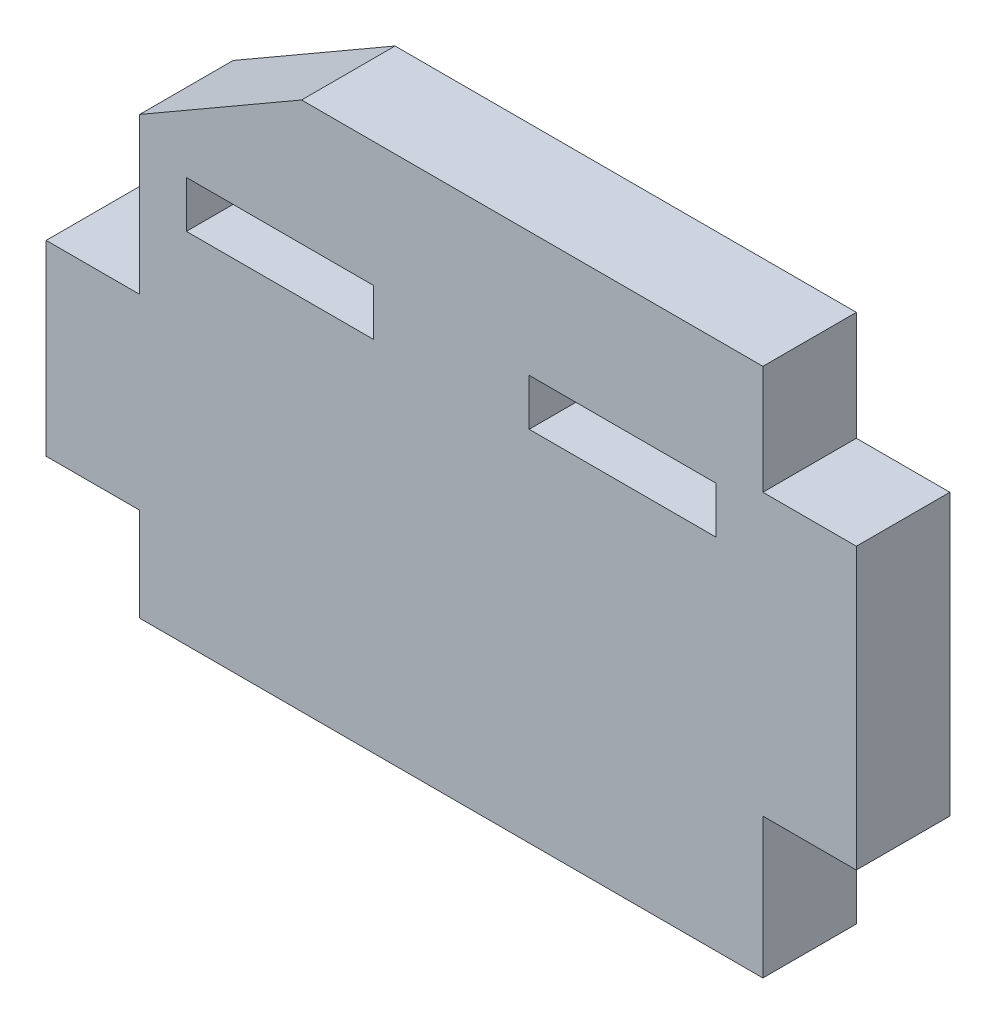
SolidWorks part; units mm, degrees
material "Plywood"
ref_plane "Plan de face" through (0, 0, 0) normal (0, 0, 1) x (1, 0, 0)
ref_plane "Plan de dessus" through (0, 0, 0) normal (0, 1, 0) x (1, 0, 0)
ref_plane "Plan de droite" through (0, 0, 0) normal (1, 0, 0) x (0, 0, -1)
sketch "Esquisse1" plane through (0, 0, 0) normal (0, 0, 1) x (1, 0, 0)
  line L1 (0, 0) -> (52, 0)
  line L2 (0, 0) -> (0, 34)
  line L3 (0, 34) -> (52, 34)
  line L4 (52, 0) -> (52, 34)
  dimension "D1" = 52
  dimension "D2" = 34
extrude "Boss.-Extru.1" add sketch "Esquisse1" along normal blind 6
sketch "Esquisse2" plane through (0, 0, 6) normal (0, 0, 1) x (1, 0, 0)
  line L1 (52, 34) -> (46, 34)
  line L2 (52, 34) -> (52, 27)
  line L3 (52, 27) -> (46, 27)
  line L4 (46, 34) -> (46, 27)
  line L5 (52, 0) -> (46, 0)
  line L6 (52, 0) -> (52, 9)
  line L7 (52, 9) -> (46, 9)
  line L8 (46, 0) -> (46, 9)
  line L9 (0, 34) -> (6, 34)
  line L10 (0, 34) -> (0, 18)
  line L11 (0, 18) -> (6, 18)
  line L12 (6, 34) -> (6, 18)
  line L13 (0, 0) -> (6, 0)
  line L14 (0, 0) -> (0, 6)
  line L15 (0, 6) -> (6, 6)
  line L16 (6, 0) -> (6, 6)
extrude "Enlèv. mat.-Extru.1" cut sketch "Esquisse2" against normal through all
sketch "Esquisse3" plane through (0, 0, 6) normal (0, 0, 1) x (1, 0, 0)
  line L1 (9, 26) -> (21, 26)
  line L2 (9, 26) -> (9, 23)
  line L3 (9, 23) -> (21, 23)
  line L4 (21, 26) -> (21, 23)
  line L5 (31, 26) -> (43, 26)
  line L6 (31, 26) -> (31, 23)
  line L7 (31, 23) -> (43, 23)
  line L8 (43, 26) -> (43, 23)
extrude "Enlèv. mat.-Extru.2" cut sketch "Esquisse3" against normal through all both and the other way through all
chamfer "Chanfrein1" distance 6 angle 60 1 edges at (6, 34, 3) first distance on face at (6, 26, 3)
